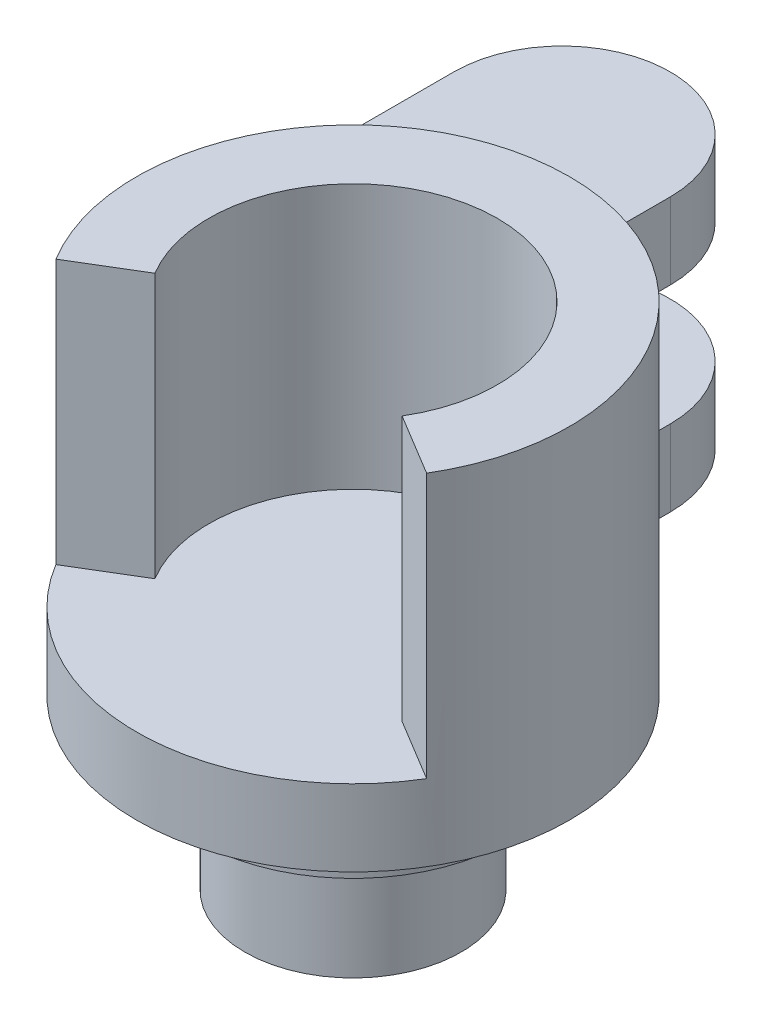
SolidWorks part; units mm, degrees
ref_plane "Front Plane" through (0, 0, 0) normal (0, 0, 1) x (1, 0, 0)
ref_plane "Top Plane" through (0, 0, 0) normal (0, 1, 0) x (1, 0, 0)
ref_plane "Right Plane" through (0, 0, 0) normal (1, 0, 0) x (0, 0, -1)
sketch "Sketch1" plane through (0, 0, 0) normal (0, 1, 0) x (1, 0, 0)
  circle A0 centre (0, 0) radius 9
  dimension "D1" = 18
extrude "Boss-Extrude1" add sketch "Sketch1" along normal blind 3.175
sketch "Sketch2" plane through (0, 3.175, 0) normal (0, 1, 0) x (1, 0, 0)
  line L0 (-7.7077, -4.6466) -> (-5.1385, -3.0978)
  line L1 (-7.7077, -4.6466) -> (7.7077, -4.6466) construction
  line L3 (5.1385, -3.0978) -> (7.7077, -4.6466)
  arc A0 (-7.7077, -4.6466) -> (7.7077, -4.6466) centre (0, 0) cw
  circle A1 centre (0, 0) radius 9 construction
  arc A2 (-5.1385, -3.0978) -> (5.1385, -3.0978) centre (0, 0) cw
  dimension "D1" = 117.832
  dimension "D2" = 3
extrude "Boss-Extrude2" add sketch "Sketch2" along normal blind 11
sketch "Sketch3" plane through (0, 0, 0) normal (0, -1, 0) x (1, 0, 0)
  circle A0 centre (0, 0) radius 6.5
  dimension "D1" = 13
extrude "Boss-Extrude3" add sketch "Sketch3" along normal blind 2
sketch "Sketch4" plane through (0, -2, 0) normal (0, -1, 0) x (1, 0, 0)
  circle A0 centre (0, 0) radius 4.5
  dimension "D1" = 9
extrude "Boss-Extrude4" add sketch "Sketch4" along normal blind 5
sketch "Sketch6" plane through (0, 0, 0) normal (0, 1, 0) x (1, 0, 0)
  line L0 (-9, 0) -> (-9, 13.1942)
  line L1 (0, 9) -> (0, 13.1942)
  arc A0 (7.7077, -4.6466) -> (-7.7077, -4.6466) centre (0, 0) ccw construction
  arc A1 (0, 13.1942) -> (-9, 13.1942) centre (-4.5, 13.1942) ccw
  arc A2 (0, 9) -> (-9, 0) centre (0, 0) ccw
  point P10 (-4.5, 17.6942)
  dimension "D1" = 8.6942
extrude "Boss-Extrude5" add sketch "Sketch6" along normal up to surface (3.175 mm away) up to face at (0, 3.175, 2.6861)
ref_plane "Plane1" through (0, 8.175, 0) normal (0, 1, 0) x (1, 0, 0)
sketch "Sketch7" plane through (0, 8.175, 0) normal (0, 1, 0) x (1, 0, 0)
  line L0 (0, 9) -> (0, 13.1942) construction
  line L1 (-9, 13.1942) -> (-9, 0) construction
  line L2 (0, 9) -> (0, 13.1942)
  line L3 (-9, 13.1942) -> (-9, 0)
  arc A0 (0, 9) -> (-9, 0) centre (0, 0) ccw construction
  arc A1 (0, 13.1942) -> (-9, 13.1942) centre (-4.5, 13.1942) ccw construction
  arc A2 (0, 9) -> (-9, 0) centre (0, 0) ccw
  arc A3 (0, 13.1942) -> (-9, 13.1942) centre (-4.5, 13.1942) ccw
extrude "Boss-Extrude7" add sketch "Sketch7" along normal blind 3.175
